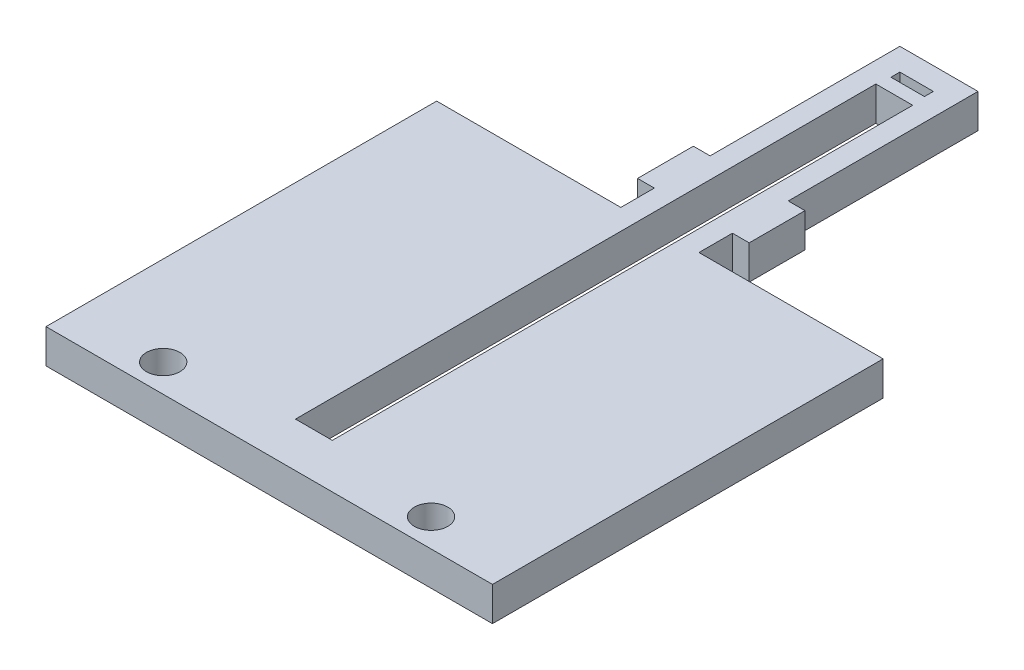
SolidWorks part; units mm, degrees
ref_plane "Front Plane" through (0, 0, 0) normal (0, 0, 1) x (1, 0, 0)
ref_plane "Top Plane" through (0, 0, 0) normal (0, 1, 0) x (1, 0, 0)
ref_plane "Right Plane" through (0, 0, 0) normal (1, 0, 0) x (0, 0, -1)
sketch "Sketch1" plane through (0, 0, 0) normal (0, 1, 0) x (1, 0, 0)
  line L1 (0, 0) -> (40, 0)
  line L2 (0, 0) -> (0, 60)
  line L3 (0, 60) -> (40, 60)
  line L4 (40, 0) -> (40, 60)
  dimension "D1" = 40
  dimension "D2" = 60
extrude "Boss-Extrude1" add sketch "Sketch1" along normal blind 3.05 contours L2 | L1 L4 L3 L2 | L4 region at (20, 0, -30)
sketch "Sketch4" plane through (0, 3.05, 0) normal (0, 1, 0) x (1, 0, 0)
  line L0 (20, 60) -> (20, 58)
  line L1 (0, 60) -> (40, 60) construction
  line L3 (21.5, 58) -> (18.5, 58)
  line L4 (18.5, 58) -> (18.5, 57.2)
  line L5 (18.5, 57.2) -> (21.5, 57.2)
  line L6 (21.5, 57.2) -> (21.5, 58)
  line L7 (20, 57.2) -> (20, 56)
  line L9 (21.65, 56) -> (18.35, 56)
  line L10 (18.35, 56) -> (18.35, 4)
  line L11 (18.35, 4) -> (21.65, 4)
  line L12 (21.65, 4) -> (21.65, 56)
  point P10 (20, 58)
  point P22 (20, 56)
  dimension "D1" = 2
  dimension "D2" = 0.8
  dimension "D3" = 1.2
  dimension "D4" = 3
  dimension "D5" = 52
  dimension "D6" = 3.3
extrude "Cut-Extrude1" cut sketch "Sketch4" against normal blind 10 contours L11 L12 L9 L10 | L5 L6 L3 L4 region at (20, 3.05, -57.6) region at (20, 3.05, -30)
sketch "Sketch5" plane through (0, 3.05, 0) normal (0, 1, 0) x (1, 0, 0)
  line L0 (0, 60) -> (0, 20)
  line L1 (0, 0) -> (0, 60) construction
  line L2 (0, 60) -> (15, 60)
  line L3 (0, 60) -> (40, 60) construction
  line L5 (40, 60) -> (25, 60)
  line L6 (40, 60) -> (40, 20)
  line L7 (40, 0) -> (40, 60) construction
  line L9 (15, 60) -> (15, 20)
  line L10 (15, 20) -> (0, 20)
  line L11 (25, 60) -> (25, 20)
  line L12 (25, 20) -> (40, 20)
  circle A0 centre (7.5, 27.5) radius 7.5
  circle A1 centre (32.5, 27.5) radius 7.5
  line M14 (40, 0) -> (40, 60)
  line M15 (40, 60) -> (0, 60)
  line M16 (0, 60) -> (0, 0)
  dimension "D1" = 40
  dimension "D2" = 15
  dimension "D3" = 40
  dimension "D4" = 15
extrude "Cut-Extrude2" [suppressed] cut sketch "Sketch5" against normal blind 10 contours A0 L9 M15 M16 | A0 | A0 L0 L10 | A1 L6 L11 M15 | A1 | A1 L12 M14
sketch "Sketch6" plane through (0, 3.05, 0) normal (0, 1, 0) x (1, 0, 0)
  line L0 (0, 60) -> (0, 35)
  line L1 (0, 0) -> (0, 60) construction
  line L2 (0, 60) -> (16.5, 60)
  line L3 (0, 60) -> (40, 60) construction
  line L4 (40, 60) -> (40, 35)
  line L5 (40, 0) -> (40, 60) construction
  line L6 (40, 60) -> (23.5, 60)
  line L9 (0, 35) -> (16.5, 35)
  line L12 (23.5, 35) -> (40, 35)
  line L13 (16.5, 35) -> (16.5, 38)
  line L14 (16.5, 38) -> (15, 38)
  line L15 (15, 38) -> (15, 43)
  line L16 (15, 43) -> (16.5, 43)
  line L17 (16.5, 43) -> (16.5, 60)
  line L18 (23.5, 35) -> (23.5, 38)
  line L19 (23.5, 38) -> (25, 38)
  line L20 (25, 38) -> (25, 43)
  line L21 (25, 43) -> (23.5, 43)
  line L22 (23.5, 43) -> (23.5, 60)
  dimension "D1" = 25
  dimension "D2" = 16.5
  dimension "D3" = 25
  dimension "D4" = 16.5
  dimension "D5" = 3
  dimension "D6" = 5
  dimension "D7" = 1.5
  dimension "D8" = 16.5
  dimension "D9" = 1.5
  dimension "D10" = 5
  dimension "D11" = 3
  dimension "D12" = 16.5
extrude "Cut-Extrude3" cut sketch "Sketch6" against normal blind 10
sketch "Sketch7" plane through (0, 3.05, 0) normal (0, 1, 0) x (1, 0, 0)
  line L0 (0, 0) -> (40, 0) construction
  line L1 (0, 0) -> (8, 0)
  line L2 (8, 0) -> (8, 2.5)
  line L3 (8, 2.5) -> (32, 2.5)
  circle A0 centre (8, 2.5) radius 1.5
  circle A1 centre (32, 2.5) radius 1.5
  dimension "D3" = 3
  dimension "D5" = 3
  dimension "D1" = 8
  dimension "D2" = 2.5
  dimension "D4" = 24
extrude "Cut-Extrude4" cut sketch "Sketch7" against normal blind 10 contours L3 A0 L2 | L2 A0 L3 | A1 region at (7.7878, 3.05, -2.7122) region at (32, 3.05, -3.9576) region at (8.6366, 3.05, -1.8634)
